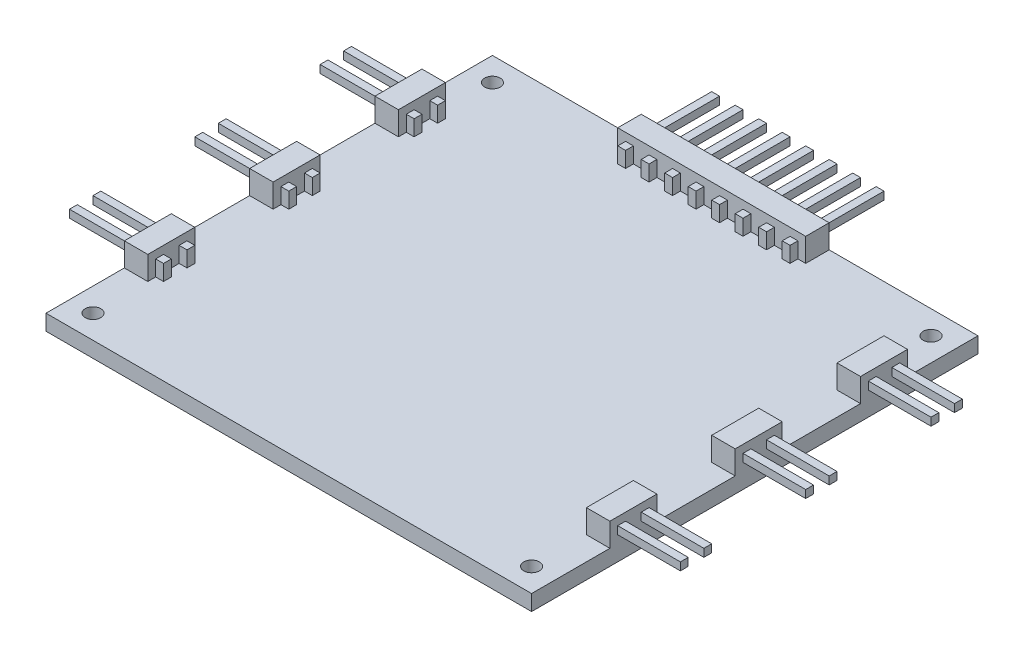
SolidWorks part; units mm, degrees
ref_plane "Front Plane" through (0, 0, 0) normal (0, 0, 1) x (1, 0, 0)
ref_plane "Top Plane" through (0, 0, 0) normal (0, 1, 0) x (1, 0, 0)
ref_plane "Right Plane" through (0, 0, 0) normal (1, 0, 0) x (0, 0, -1)
sketch "Sketch1" plane through (0, 0, 0) normal (0, 1, 0) x (1, 0, 0)
  line L1 (-24.6063, 22.6219) -> (24.6062, 22.6219)
  line L2 (-24.6063, 22.6219) -> (-24.6063, -22.6219)
  line L3 (-24.6063, -22.6219) -> (24.6062, -22.6219)
  line L4 (24.6062, 22.6219) -> (24.6062, -22.6219)
  line L5 (-24.6063, 22.6219) -> (24.6062, -22.6219) construction
  line L6 (-24.6063, -22.6219) -> (24.6062, 22.6219) construction
  point P0 (0, 0)
  dimension "D1" = 49.2125
  dimension "D2" = 45.2437
extrude "Boss-Extrude2" add sketch "Sketch1" along normal blind 1.5875
sketch "Sketch2" plane through (0, 1.5875, 0) normal (0, 1, 0) x (1, 0, 0)
  line L0 (24.6062, -22.6219) -> (24.6062, 22.6219) construction
  line L1 (21.4312, 13.8906) -> (30.9562, 13.8906)
  line L2 (21.4312, 13.8906) -> (21.4312, 14.6844)
  line L3 (21.4312, 14.6844) -> (30.9562, 14.6844)
  line L4 (30.9562, 13.8906) -> (30.9562, 14.6844)
  line L5 (21.4312, 12.3031) -> (30.9562, 12.3031)
  line L6 (21.4312, 12.3031) -> (21.4312, 11.5094)
  line L7 (21.4312, 11.5094) -> (30.9562, 11.5094)
  line L8 (30.9562, 12.3031) -> (30.9562, 11.5094)
  line L9 (24.6062, 22.6219) -> (-24.6063, 22.6219) construction
  line L10 (21.4313, 1.1906) -> (21.4313, 1.9844)
  line L11 (21.4313, 1.1906) -> (30.9563, 1.1906)
  line L12 (30.9563, 1.1906) -> (30.9563, 1.9844)
  line L13 (21.4313, 1.9844) -> (30.9563, 1.9844)
  line L14 (21.4313, -0.3969) -> (21.4313, -1.1906)
  line L15 (21.4313, -0.3969) -> (30.9563, -0.3969)
  line L16 (30.9563, -0.3969) -> (30.9563, -1.1906)
  line L17 (21.4313, -1.1906) -> (30.9563, -1.1906)
  line L18 (21.4313, -11.5094) -> (21.4313, -10.7156)
  line L19 (21.4313, -11.5094) -> (30.9563, -11.5094)
  line L20 (30.9563, -11.5094) -> (30.9563, -10.7156)
  line L21 (21.4313, -10.7156) -> (30.9563, -10.7156)
  line L22 (21.4313, -13.0969) -> (21.4313, -13.8906)
  line L23 (21.4313, -13.0969) -> (30.9563, -13.0969)
  line L24 (30.9563, -13.0969) -> (30.9563, -13.8906)
  line L25 (21.4313, -13.8906) -> (30.9563, -13.8906)
  line L26 (0, 22.6219) -> (0, -22.6219) construction
  line L27 (-24.6063, -22.6219) -> (24.6062, -22.6219) construction
  line L28 (-21.4313, -13.8906) -> (-30.9563, -13.8906)
  line L29 (-30.9563, -13.0969) -> (-30.9563, -13.8906)
  line L30 (-21.4313, -13.0969) -> (-30.9563, -13.0969)
  line L31 (-21.4313, -13.0969) -> (-21.4313, -13.8906)
  line L32 (-21.4313, -10.7156) -> (-30.9563, -10.7156)
  line L33 (-30.9563, -11.5094) -> (-30.9563, -10.7156)
  line L34 (-21.4313, -11.5094) -> (-30.9563, -11.5094)
  line L35 (-21.4313, -11.5094) -> (-21.4313, -10.7156)
  line L36 (-21.4313, -1.1906) -> (-30.9563, -1.1906)
  line L37 (-30.9563, -0.3969) -> (-30.9563, -1.1906)
  line L38 (-21.4313, -0.3969) -> (-30.9563, -0.3969)
  line L39 (-21.4313, -0.3969) -> (-21.4313, -1.1906)
  line L40 (-21.4313, 1.9844) -> (-30.9563, 1.9844)
  line L41 (-30.9563, 1.1906) -> (-30.9563, 1.9844)
  line L42 (-21.4313, 1.1906) -> (-30.9563, 1.1906)
  line L43 (-21.4313, 1.1906) -> (-21.4313, 1.9844)
  line L44 (-30.9563, 12.3031) -> (-30.9563, 11.5094)
  line L45 (-21.4313, 11.5094) -> (-30.9563, 11.5094)
  line L46 (-21.4313, 12.3031) -> (-21.4313, 11.5094)
  line L47 (-21.4313, 12.3031) -> (-30.9563, 12.3031)
  line L48 (-30.9563, 13.8906) -> (-30.9563, 14.6844)
  line L49 (-21.4313, 14.6844) -> (-30.9563, 14.6844)
  line L50 (-21.4313, 13.8906) -> (-21.4313, 14.6844)
  line L51 (-21.4313, 13.8906) -> (-30.9563, 13.8906)
  line L52 (-22.225, -10.7156) -> (-22.225, -11.5094)
  line L53 (-22.225, -13.0969) -> (-22.225, -13.8906)
  line L54 (-22.225, -0.3969) -> (-22.225, -1.1906)
  line L55 (-22.225, 1.9844) -> (-22.225, 1.1906)
  line L56 (-22.225, 12.3031) -> (-22.225, 11.5094)
  line L57 (-22.225, 14.6844) -> (-22.225, 13.8906)
  line L58 (22.225, -13.0969) -> (22.225, -13.8906)
  line L59 (22.225, -10.7156) -> (22.225, -11.5094)
  line L60 (22.225, -0.3969) -> (22.225, -1.1906)
  line L61 (22.225, 1.9844) -> (22.225, 1.1906)
  line L62 (22.225, 12.3031) -> (22.225, 11.5094)
  line L63 (22.225, 14.6844) -> (22.225, 13.8906)
  line M12 (-24.6063, 22.6219) -> (-24.6063, -22.6219)
  dimension "D1" = 0.7937
  dimension "D2" = 1.5875
  dimension "D3" = 3.175
  dimension "D4" = 9.525
  dimension "D5" = 7.9375
  dimension "D7" = 0.7937
  dimension "D6" = 3
extrude "Boss-Extrude4" add sketch "Sketch2" along normal blind 0.7937 contours L49 L57 L51 L50 | L47 L56 L45 L46 | L40 L55 L42 L43 | L38 L54 L36 L39 | L32 L52 L34 L35 | L30 L53 L28 L31 | L60 L15 L14 L17 | L61 L13 L10 L11 | L59 L21 L18 L19 | L58 L23 L22 L25 | L63 L3 L2 L1 | L62 L5 L6 L7 region at (21.8281, 1.5875, -14.2875) region at (21.8281, 1.5875, -11.9063) region at (21.8281, 1.5875, -1.5875) region at (21.8281, 1.5875, 0.7937) region at (21.8281, 1.5875, 11.1125) region at (21.8281, 1.5875, 13.4937) region at (-21.8281, 1.5875, 13.4937) region at (-21.8281, 1.5875, 11.1125) region at (-21.8281, 1.5875, 0.7937) region at (-21.8281, 1.5875, -1.5875) region at (-21.8281, 1.5875, -11.9063) region at (-21.8281, 1.5875, -14.2875)
extrude "Boss-Extrude5" add sketch "Sketch2<3>" along normal blind 0.7937 from offset 0.7937 contours L49 L57 L51 L50 | L57 L49 L51 M12 | L51 L49 L48 M12 | L47 L44 L45 M12 | L56 L47 L45 M12 | L47 L56 L45 L46 | L40 L41 L42 L43 | L38 L37 L36 L39 | L32 L33 L34 L35 | L30 L29 L28 L31 | L19 L20 L21 L18 | L25 L24 L23 L22 | L15 L16 L17 L14 | L13 L12 L11 L10 | L5 L8 L7 L6 | L3 L4 L1 L2 region at (-27.7813, 1.5875, -14.2875) region at (-23.4156, 1.5875, -14.2875) region at (-27.7813, 1.5875, -11.9062) region at (-23.4156, 1.5875, -11.9063) region at (-21.8281, 1.5875, -11.9062) region at (-21.8281, 1.5875, -14.2875)
sketch "Sketch2<3>" plane through (0, 1.5875, 0) normal (0, 1, 0) x (1, 0, 0) same geometry as "Sketch2"
sketch "Sketch3" plane through (0, 1.5875, 0) normal (0, 1, 0) x (1, 0, 0)
  line L0 (-24.6063, 22.6219) -> (-24.6063, -22.6219) construction
  line L1 (-24.6063, 10.7156) -> (-22.225, 10.7156)
  line L2 (-24.6063, 10.7156) -> (-24.6063, 15.4781)
  line L3 (-24.6063, 15.4781) -> (-22.225, 15.4781)
  line L4 (-22.225, 10.7156) -> (-22.225, 15.4781)
  line L5 (-21.4313, 11.5094) -> (-30.9563, 11.5094) construction
  line L6 (-21.4313, 14.6844) -> (-30.9563, 14.6844) construction
  line L7 (-24.6062, -1.9844) -> (-24.6062, 2.7781)
  line L8 (-24.6062, -1.9844) -> (-22.225, -1.9844)
  line L9 (-22.225, -1.9844) -> (-22.225, 2.7781)
  line L10 (-24.6062, 2.7781) -> (-22.225, 2.7781)
  line L11 (-24.6062, -14.6844) -> (-24.6062, -9.9219)
  line L12 (-24.6062, -14.6844) -> (-22.225, -14.6844)
  line L13 (-22.225, -14.6844) -> (-22.225, -9.9219)
  line L14 (-24.6062, -9.9219) -> (-22.225, -9.9219)
  line L15 (0, 22.6219) -> (0, -22.6219) construction
  line L16 (24.6062, 22.6219) -> (-24.6063, 22.6219) construction
  line L17 (-24.6063, -22.6219) -> (24.6062, -22.6219) construction
  line L18 (24.6062, -9.9219) -> (22.225, -9.9219)
  line L19 (22.225, -14.6844) -> (22.225, -9.9219)
  line L20 (24.6062, -14.6844) -> (22.225, -14.6844)
  line L21 (24.6062, -14.6844) -> (24.6062, -9.9219)
  line L22 (24.6062, 2.7781) -> (22.225, 2.7781)
  line L23 (22.225, -1.9844) -> (22.225, 2.7781)
  line L24 (24.6062, -1.9844) -> (22.225, -1.9844)
  line L25 (24.6062, -1.9844) -> (24.6062, 2.7781)
  line L26 (22.225, 10.7156) -> (22.225, 15.4781)
  line L27 (24.6062, 15.4781) -> (22.225, 15.4781)
  line L28 (24.6062, 10.7156) -> (24.6062, 15.4781)
  line L29 (24.6062, 10.7156) -> (22.225, 10.7156)
  dimension "D1" = 0.7937
  dimension "D2" = 0.7937
  dimension "D3" = 2.3813
  dimension "D4" = 3
extrude "Boss-Extrude6" add sketch "Sketch3" along normal blind 2.3813
sketch "Sketch4" plane through (0, 1.5875, 0) normal (0, 1, 0) x (1, 0, 0)
  line L0 (0, 22.6219) -> (0, 0) construction
  line L1 (24.6062, 22.6219) -> (-24.6063, 22.6219) construction
  line L2 (8.7312, 19.4469) -> (8.7312, 28.9719)
  line L3 (-0.7938, 19.4469) -> (-1.5875, 19.4469)
  line L4 (-0.7938, 19.4469) -> (-0.7938, 28.9719)
  line L5 (-0.7938, 28.9719) -> (-1.5875, 28.9719)
  line L6 (-1.5875, 19.4469) -> (-1.5875, 28.9719)
  line L7 (-3.175, 19.4469) -> (-3.9688, 19.4469)
  line L8 (-3.175, 19.4469) -> (-3.175, 28.9719)
  line L9 (-3.175, 28.9719) -> (-3.9688, 28.9719)
  line L10 (-3.9688, 19.4469) -> (-3.9688, 28.9719)
  line L11 (-5.5563, 19.4469) -> (-6.35, 19.4469)
  line L12 (-5.5563, 19.4469) -> (-5.5563, 28.9719)
  line L13 (-5.5563, 28.9719) -> (-6.35, 28.9719)
  line L14 (-6.35, 19.4469) -> (-6.35, 28.9719)
  line L15 (-7.9375, 19.4469) -> (-8.7313, 19.4469)
  line L16 (-7.9375, 19.4469) -> (-7.9375, 28.9719)
  line L17 (-7.9375, 28.9719) -> (-8.7313, 28.9719)
  line L18 (-8.7313, 19.4469) -> (-8.7313, 28.9719)
  line L19 (7.9375, 28.9719) -> (8.7312, 28.9719)
  line L20 (7.9375, 19.4469) -> (7.9375, 28.9719)
  line L21 (7.9375, 19.4469) -> (8.7312, 19.4469)
  line L22 (6.35, 19.4469) -> (6.35, 28.9719)
  line L23 (5.5562, 28.9719) -> (6.35, 28.9719)
  line L24 (5.5562, 19.4469) -> (5.5562, 28.9719)
  line L25 (5.5562, 19.4469) -> (6.35, 19.4469)
  line L26 (3.9687, 19.4469) -> (3.9687, 28.9719)
  line L27 (3.175, 28.9719) -> (3.9687, 28.9719)
  line L28 (3.175, 19.4469) -> (3.175, 28.9719)
  line L29 (3.175, 19.4469) -> (3.9687, 19.4469)
  line L30 (1.5875, 19.4469) -> (1.5875, 28.9719)
  line L31 (0.7937, 28.9719) -> (1.5875, 28.9719)
  line L32 (0.7937, 19.4469) -> (0.7937, 28.9719)
  line L33 (0.7937, 19.4469) -> (1.5875, 19.4469)
  line L34 (-8.7313, 20.2406) -> (-7.9375, 20.2406)
  line L35 (-6.35, 20.2406) -> (-5.5563, 20.2406)
  line L36 (-3.9688, 20.2406) -> (-3.175, 20.2406)
  line L37 (-1.5875, 20.2406) -> (-0.7938, 20.2406)
  line L38 (0.7938, 20.2406) -> (1.5875, 20.2406)
  line L39 (3.175, 20.2406) -> (3.9688, 20.2406)
  line L40 (5.5563, 20.2406) -> (6.35, 20.2406)
  line L41 (7.9375, 20.2406) -> (8.7313, 20.2406)
  dimension "D1" = 1.5875
  dimension "D2" = 1.5875
  dimension "D3" = 1.5875
  dimension "D4" = 0.7937
  dimension "D5" = 1.5875
  dimension "D6" = 3.175
  dimension "D7" = 6.35
  dimension "D8" = 0.7937
extrude "Boss-Extrude7" add sketch "Sketch4" along normal blind 0.7937 contours L34 L18 L15 L16 | L35 L14 L11 L12 | L36 L10 L7 L8 | L37 L6 L3 L4 | L38 L32 L33 L30 | L39 L28 L29 L26 | L40 L24 L25 L22 | L41 L20 L21 L2 region at (8.3344, 1.5875, -19.8438) region at (-1.1906, 1.5875, -19.8438) region at (-3.5719, 1.5875, -19.8438) region at (-5.9531, 1.5875, -19.8438) region at (-8.3344, 1.5875, -19.8438) region at (5.9531, 1.5875, -19.8438) region at (3.5719, 1.5875, -19.8438) region at (1.1906, 1.5875, -19.8438)
extrude "Boss-Extrude8" add sketch "Sketch4<3>" along normal blind 0.7937 from offset 0.7937 contours L16 L17 L18 L15 | L12 L13 L14 L11 | L8 L9 L10 L7 | L4 L5 L6 L3 | L30 L31 L32 L33 | L26 L27 L28 L29 | L22 L23 L24 L25 | L2 L19 L20 L21
sketch "Sketch4<3>" plane through (0, 1.5875, 0) normal (0, 1, 0) x (1, 0, 0) same geometry as "Sketch4"
sketch "Sketch5" plane through (0, 1.5875, 0) normal (0, 1, 0) x (1, 0, 0)
  line L0 (24.6062, 22.6219) -> (-24.6063, 22.6219) construction
  line L1 (-9.525, 22.6219) -> (9.525, 22.6219)
  line L2 (-9.525, 22.6219) -> (-9.525, 20.2406)
  line L3 (-9.525, 20.2406) -> (9.525, 20.2406)
  line L4 (9.525, 22.6219) -> (9.525, 20.2406)
  line L5 (-8.7313, 19.4469) -> (-8.7313, 28.9719) construction
  line L6 (8.7312, 19.4469) -> (8.7312, 28.9719) construction
  dimension "D1" = 2.3813
  dimension "D2" = 0.7937
  dimension "D3" = 0.7937
extrude "Boss-Extrude9" add sketch "Sketch5" along normal blind 2.3813
sketch "Sketch12" plane through (0, 1.5875, 0) normal (0, 1, 0) x (1, 0, 0)
  line L0 (-9.525, 22.6219) -> (-24.6063, 22.6219) construction
  line L1 (-24.6063, 22.6219) -> (-24.6063, 15.4781) construction
  line L2 (-22.225, 20.2406) -> (-22.225, -20.2406) construction
  line L3 (-22.225, -20.2406) -> (22.225, -20.2406) construction
  line L4 (22.225, -20.2406) -> (22.225, 20.2406) construction
  line L5 (22.225, 20.2406) -> (-22.225, 20.2406) construction
  line L6 (24.6062, 15.4781) -> (24.6062, 22.6219) construction
  line L7 (-24.6063, -22.6219) -> (24.6062, -22.6219) construction
  circle A0 centre (-22.225, 20.2406) radius 0.7937
  circle A1 centre (-22.225, -20.2406) radius 0.7937
  circle A2 centre (22.225, -20.2406) radius 0.7937
  circle A3 centre (22.225, 20.2406) radius 0.7937
  dimension "D1" = 1.5875
  dimension "D2" = 2.3813
  dimension "D3" = 2.3813
  dimension "D4" = 2.3813
  dimension "D5" = 2.3813
extrude "Cut-Extrude1" cut sketch "Sketch12" against normal through all
